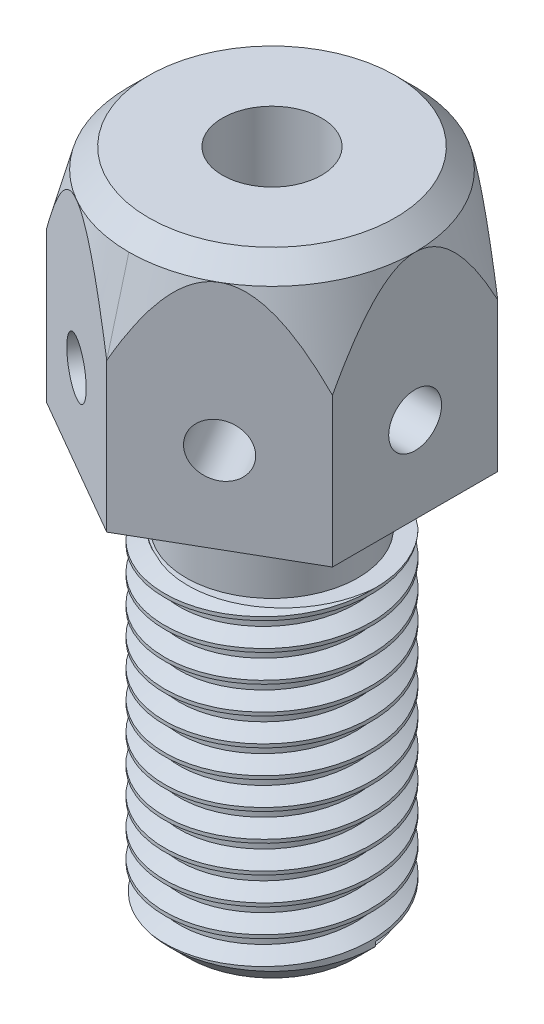
SolidWorks part; units mm, degrees
ref_plane "Front Plane" through (0, 0, 0) normal (0, 0, 1) x (1, 0, 0)
ref_plane "Top Plane" through (0, 0, 0) normal (0, 1, 0) x (1, 0, 0)
ref_plane "Right Plane" through (0, 0, 0) normal (1, 0, 0) x (0, 0, -1)
sketch "Sketch2" plane through (0, 0, 0) normal (0, 1, 0) x (1, 0, 0)
  circle A0 centre (0, 0) radius 3.9688
  dimension "D1" = 7.9375
extrude "Boss-Extrude1" add sketch "Sketch2" along normal blind 12.7
chamfer "Chamfer1" distance 0.762 angle 45 1 edges at (0, 0, 3.9688)
thread "Thread1" pitch 1.0583 method cut profile "Thread Profile1" start angle 0, offset 0, length 12.7, pitch 1.0583, diameter 7.9375
ref_plane "Plane1" through (3.9688, 0, 0) normal (0, 0, 1) x (1, 0, 0)
sketch "Thread Profile1" plane through (3.9688, 0, 0) normal (0, 0, 1) x (1, 0, 0)
  line L0 (0, 0) -> (0, 1.0583) construction
  line L11 (0, 0) -> (0, 0.926)
  line L12 (0, 0.926) -> (-0.5728, 0.5953)
  line L13 (-0.5728, 0.5953) -> (-0.5728, 0.3307)
  line L15 (-0.5728, 0.3307) -> (0, 0)
  line L17 (-0.5728, 0.463) -> (0, 0.463) construction
  point P2 (0, 0)
  dimension "Pitch" = 1.0583
  dimension "Profile_Angle" = 60
  dimension "Profile_Land" = 0.2646
  dimension "Profile_Height" = 0.5728
sketch "Sketch6" plane through (0, 12.7, 0) normal (0, 1, 0) x (1, 0, 0)
  circle A0 centre (0, 0) radius 3.302
  dimension "D1" = 6.604
extrude "Boss-Extrude2" add sketch "Sketch6" along normal blind 3.048
sketch "Sketch8" plane through (0, 15.748, 0) normal (0, 1, 0) x (1, 0, 0)
  line L1 (0, -6.35) -> (5.4993, -3.175)
  line L2 (5.4993, -3.175) -> (5.4993, 3.175)
  line L3 (5.4993, 3.175) -> (0, 6.35)
  line L4 (0, 6.35) -> (-5.4993, 3.175)
  line L5 (-5.4993, 3.175) -> (-5.4993, -3.175)
  line L6 (-5.4993, -3.175) -> (0, -6.35)
  circle A0 centre (0, 0) radius 6.35 construction
  dimension "D1" = 12.7
extrude "Boss-Extrude3" add sketch "Sketch8" along normal blind 8.89
sketch "Sketch9" plane through (0, 24.638, 0) normal (0, 1, 0) x (1, 0, 0)
  circle A0 centre (0, 0) radius 1.905
  dimension "D1" = 3.81
extrude "Cut-Extrude1" cut sketch "Sketch9" against normal blind 7.874
sketch "Sketch10" plane through (-2.7496, 0, -4.7625) normal (-0.5, 0, -0.866) x (-0.866, 0, 0.5)
  line L0 (3.302, 12.7) -> (-3.302, 12.7) construction
  line L3 (0, 15.748) -> (0, 24.638) construction
  line L4 (-3.175, 15.748) -> (3.175, 15.748) construction
  line L5 (-3.175, 24.638) -> (3.175, 24.638) construction
  circle A0 centre (0, 19.05) radius 1.016
  point P4 (0, 0)
  point P5 (0, 0)
  dimension "D1" = 2.032
  dimension "D2" = 6.35
extrude "Cut-Extrude2" cut sketch "Sketch10" against normal blind 6.35
pattern_circular "CirPattern1" count 6 over 360 about axis through (0, 24.638, 0) along (0, 1, 0) of "Cut-Extrude2"
sketch "Sketch12" plane through (0, 24.638, 0) normal (0, 1, 0) x (1, 0, 0)
  line L0 (5.4993, -3.175) -> (5.4993, 3.175) construction
  circle A0 centre (0, 0) radius 5.4993
sketch "Sketch11" plane through (0, 0, 0) normal (1, 0, 0) x (0, 0, -1)
  line L7 (-6.35, 24.638) -> (-5.4993, 24.638)
  line L8 (-6.35, 24.638) -> (-3.175, 24.638) construction
  line L9 (-5.4993, 24.638) -> (-6.35, 21.463)
  line L10 (-6.35, 24.638) -> (-6.35, 15.748) construction
  line L11 (-6.35, 21.463) -> (-6.35, 24.638)
  point P7 (0, 0)
  dimension "D2" = 75
sweep "Cut-Sweep2" cut profiles "Sketch11" path "Sketch12"
sketch "Sketch13" plane through (0, 24.638, 0) normal (0, 1, 0) x (1, 0, 0)
  circle A0 centre (0, 0) radius 5.4993
  arc A1 (-5.4993, 0) -> (-2.7496, -4.7625) centre (0, 0) ccw construction
  circle A2 centre (0, 0) radius 1.905
  circle A3 centre (0, 0) radius 1.905 construction
extrude "Boss-Extrude4" add sketch "Sketch13" along normal blind 0.762
chamfer "Chamfer2" distance 0.762 angle 45 1 edges at (0, 25.4, 5.4993)
